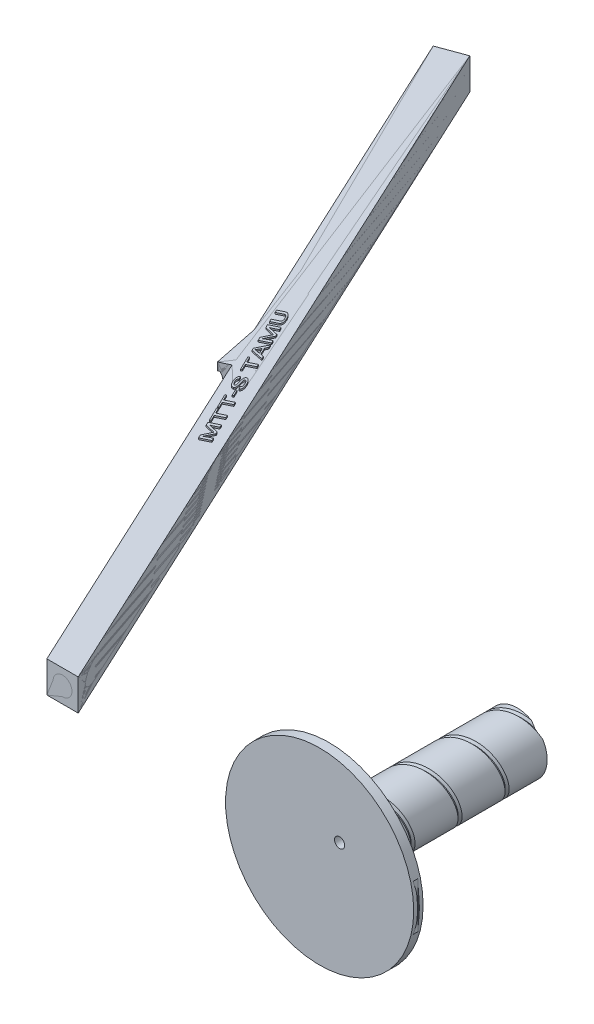
SolidWorks part; units mm, degrees
other "Markup1"
sketch "Sketch47" plane through (-252.8035, -252.8035, 139.7467) normal (0, 0, 1) x (-1, 0, 0)
ref_plane "Front Plane" through (0, 0, 0) normal (1, 0, 0) x (0, 1, 0)
ref_plane "Top Plane" through (0, 0, 0) normal (0, 0, 1) x (0, 1, 0)
ref_plane "Right Plane" through (0, 0, 0) normal (0, 1, 0) x (-1, 0, 0)
sketch "Sketch8" plane through (0, 0, 0) normal (0, 0, 1) x (0, 1, 0)
  circle A0 centre (0, 0) radius 9.55
  dimension "D1" = 19.1
extrude "HelicalLength" add sketch "Sketch8" along normal blind 60 separate body
thread "WireThreads" pitch 1.5 method cut profile "Thread Profile1" start angle 14, offset 2, length 160, pitch 15, diameter 19.1
ref_plane "Plane1" through (9.2663, 2.3104, -2) normal (0.2419, -0.9703, 0) x (0.9703, 0.2419, 0)
sketch "Thread Profile1" plane through (9.2663, 2.3104, -2) normal (0.2419, -0.9703, 0) x (0.9703, 0.2419, 0)
  line L0 (0, 0) -> (0, 1.5) construction
  line L11 (0, 0) -> (0, 1.3125)
  line L12 (0, 1.3125) -> (-0.8119, 0.8437)
  line L13 (-0.8119, 0.8437) -> (-0.8119, 0.4687)
  line L15 (-0.8119, 0.4687) -> (0, 0)
  line L17 (-0.8119, 0.6562) -> (0, 0.6562) construction
  point P2 (0, 0)
  dimension "Pitch" = 1.5
  dimension "Profile_Angle" = 60
  dimension "Profile_Land" = 0.375
  dimension "Profile_Height" = 0.8119
sketch "Sketch12" plane through (0, 0, 0) normal (0, 0, 1) x (0, 1, 0)
  circle A0 centre (0, 0) radius 8
extrude "Cut-Extrude1" cut sketch "Sketch12" along normal blind 60
sketch "Sketch14" plane through (0, 0, 60) normal (0, 0, 1) x (0, -1, 0)
  circle A0 centre (0, 0) radius 30
extrude "Top of Helical" add sketch "Sketch14" along normal blind 3 contours A0
sketch "Supports" plane through (0, 0, 0) normal (0, 1, 0) x (-1, 0, 0)
  line L2 (83.0856, 56.8881) -> (192.1707, -177.0456)
  line L11 (200.7103, -173.9139) -> (93.0856, 56.8881)
  line L12 (93.0856, 56.8881) -> (83.0856, 56.8881)
  line L13 (192.1707, -177.0456) -> (200.7103, -173.9139)
  line L15 (144.6827, -53.7621) -> (147.8613, -52.2799)
  line L16 (147.8613, -52.2799) -> (150.8999, -67.095)
  line L18 (150.8999, -67.095) -> (144.6827, -53.7621)
  point P0 (0, 0)
  point P1 (0, 0)
  point P2 (0, 0)
extrude "Support" add sketch "Supports" along normal mid plane 10 contours L2 L13 L11 L12 | L16 L15 L11
sketch "Sketch18" plane through (0, 0, 63) normal (0, 0, 1) x (0, -1, 0)
  circle A0 centre (-7.0243, 6.3716) radius 1.6161
extrude "SMAHole" cut sketch "Sketch18" against normal blind 3
sketch "Sketch30" plane through (0, 0, 0) normal (1, 0, 0) x (0, 1, 0)
  line L0 (150.6912, -172.7061) -> (149.5087, -173.9919)
  line L1 (0, -188.7392) -> (0, 188.7392) construction
  line L2 (-150.6912, -172.7061) -> (-149.5087, -173.9919)
sketch "Sketch40" plane through (0, 0, 0) normal (0, 1, 0) x (-1, 0, 0)
  line L0 (0, 189.6665) -> (0, -189.6665) construction
  line L1 (-30.0176, 61.2136) -> (-30.0176, 61.7977)
  line L2 (-29.7091, 61.7977) -> (-30.0176, 61.7977)
  line L3 (-29.0913, 62.3087) -> (-29.7091, 61.7977)
  line L4 (-29.0913, 60.7506) -> (-29.0913, 62.3087)
  line L5 (30.0176, 61.2136) -> (29.6894, 61.2136)
  line L6 (29.6894, 61.2136) -> (29.0913, 60.7506)
  line L7 (29.0913, 60.7506) -> (29.0913, 62.3087)
  line L8 (29.0913, 62.3087) -> (29.7091, 61.7977)
  line L9 (29.7091, 61.7977) -> (30.0176, 61.7977)
  line L10 (30.0176, 61.2136) -> (30.0176, 61.7977)
  line L11 (-29.6894, 61.2136) -> (-29.0913, 60.7506)
  line L12 (-30.0176, 61.2136) -> (-29.6894, 61.2136)
extrude "Cut-Extrude6" cut sketch "Sketch40" against normal mid plane 30
sketch "Sketch41" plane through (-46.4333, 0, -99.5766) normal (0.4226, 0, 0.9063) x (0.9063, 0, -0.4226)
  circle A0 centre (-115.2305, 0) radius 4.6444
extrude "Cut-Extrude7" cut sketch "Sketch41" against normal blind 15
sketch "Sketch42" plane through (0, 5, 0) normal (0, 1, 0) x (-1, 0, 0)
  line L0 (126.2063, -28.5433) -> (156.3015, -91.4697) construction
  text T0 "<b>MTT-S TAMU</b>" font "Roboto" height 3.175
sketch "Sketch43" plane through (0, 5, 0) normal (0, 1, 0) x (-1, 0, 0)
  line L0 (101.9085, 20.9352) -> (104.9898, 21.8732)
  line L1 (104.9898, 21.8732) -> (103.2157, 19.5777)
  line L2 (103.2157, 19.5777) -> (106.1118, 19.4956)
  line L3 (106.1118, 19.4956) -> (103.4237, 17.7047)
  line L4 (103.4237, 17.7047) -> (103.3006, 18.002)
  line L5 (103.3006, 18.002) -> (105.2049, 19.233)
  line L6 (105.2049, 19.233) -> (102.6528, 19.3054)
  line L7 (102.6528, 19.3054) -> (104.2052, 21.3141)
  line L8 (104.2052, 21.3141) -> (102.0446, 20.6563)
  line L9 (102.0446, 20.6563) -> (101.9085, 20.9352)
  line L10 (104.0107, 16.514) -> (106.5727, 17.7315)
  line L11 (106.5727, 17.7315) -> (106.8818, 17.0809)
  line L12 (106.8818, 17.0809) -> (107.1603, 17.2133)
  line L13 (107.1603, 17.2133) -> (106.4169, 18.7774)
  line L14 (106.4169, 18.7774) -> (106.1419, 18.6467)
  line L15 (106.1419, 18.6467) -> (106.4409, 18.0177)
  line L16 (106.4409, 18.0177) -> (103.8755, 16.7985)
  line L17 (103.8755, 16.7985) -> (104.0107, 16.514)
  line L18 (106.9455, 16.9655) -> (107.25, 16.3249)
  line L19 (107.25, 16.3249) -> (104.6808, 15.1039)
  line L20 (104.6808, 15.1039) -> (104.8254, 14.7998)
  line L21 (104.8254, 14.7998) -> (107.3884, 16.0179)
  line L22 (107.3884, 16.0179) -> (107.6844, 15.3948)
  line L23 (107.6844, 15.3948) -> (107.9593, 15.5255)
  line L24 (107.9593, 15.5255) -> (107.2149, 17.0917)
  line L25 (107.2149, 17.0917) -> (106.9455, 16.9655)
  line L26 (106.5727, 12.8032) -> (106.3025, 12.9886)
  line L27 (109.0001, 12.2749) -> (108.7224, 12.4151)
  line L28 (109.7957, 10.8368) -> (110.1001, 10.1962)
  line L29 (110.1001, 10.1962) -> (107.531, 8.9752)
  line L30 (107.531, 8.9752) -> (107.6755, 8.6712)
  line L31 (107.6755, 8.6712) -> (110.2385, 9.8892)
  line L32 (110.2385, 9.8892) -> (110.5346, 9.2662)
  line L33 (110.5346, 9.2662) -> (110.8094, 9.3968)
  line L34 (110.8094, 9.3968) -> (110.0651, 10.963)
  line L35 (110.0651, 10.963) -> (109.7957, 10.8368)
  line L36 (109.4678, 4.7772) -> (112.5491, 5.7152)
  line L37 (112.5491, 5.7152) -> (110.775, 3.4198)
  line L38 (110.775, 3.4198) -> (113.6711, 3.3376)
  line L39 (113.6711, 3.3376) -> (110.9831, 1.5467)
  line L40 (110.9831, 1.5467) -> (110.8599, 1.8441)
  line L41 (110.8599, 1.8441) -> (112.7642, 3.0751)
  line L42 (112.7642, 3.0751) -> (110.2121, 3.1475)
  line L43 (110.2121, 3.1475) -> (111.7646, 5.1561)
  line L44 (111.7646, 5.1561) -> (109.6039, 4.4984)
  line L45 (109.6039, 4.4984) -> (109.4678, 4.7772)
  line L46 (109.6778, 7.5921) -> (110.9514, 7.5921)
  line L47 (110.9514, 7.5921) -> (110.1423, 6.596)
  line L48 (110.1423, 6.596) -> (109.6778, 7.5921)
  line L49 (108.2031, 7.5921) -> (109.3354, 7.5921)
  line L50 (109.3354, 7.5921) -> (109.9101, 6.3599)
  line L51 (109.9101, 6.3599) -> (109.1793, 5.4602)
  line L52 (109.1793, 5.4602) -> (109.3354, 5.1255)
  line L53 (109.3354, 5.1255) -> (111.6176, 7.8904)
  line L54 (111.6176, 7.8904) -> (108.0755, 7.8904)
  line L55 (108.0755, 7.8904) -> (108.2031, 7.5921)
  line L56 (114.1273, 2.3932) -> (114.2581, 2.1081)
  line L57 (114.8933, 0.7892) -> (115.0089, 0.4737)
  line L58 (106.3776, 14.5474) -> (106.8818, 13.4741)
  line L59 (106.8818, 13.4741) -> (106.6452, 13.3629)
  line L60 (106.6452, 13.3629) -> (106.1346, 14.4333)
  line L61 (106.1346, 14.4333) -> (106.3776, 14.5474)
  spline S0 degree 3 poles (109.0001, 12.2749) (109.3075, 12.5936) (109.2657, 13.5749) (108.1151, 13.7916) (107.6133, 13.0938) (107.5354, 12.4103) (107.2883, 11.5281) (106.4624, 11.6885) (106.2609, 12.2706) (106.4283, 12.618) (106.5727, 12.8032) knots 0 0 0 0 0.216001 0.35012 0.454376 0.59346 0.711588 0.832522 0.880345 1 1 1 1
  spline S1 degree 3 poles (106.3025, 12.9886) (106.1901, 12.7865) (105.9616, 12.4602) (106.0391, 11.9135) (106.2897, 11.5153) (106.8216, 11.2348) (107.4632, 11.4221) (107.798, 11.9958) (107.9019, 12.5768) (107.972, 13.1456) (108.4276, 13.4453) (108.9775, 13.1301) (108.8433, 12.6139) (108.7224, 12.4151) knots 0 0 0 0 0.1187 0.173526 0.2599 0.338136 0.450558 0.543453 0.645861 0.740559 0.809819 0.869876 1 1 1 1
  spline S2 degree 3 poles (114.2581, 2.1081) (113.715, 1.888) (113.0487, 1.4788) (112.0912, 1.1645) (111.7302, 0.563) (112.0143, -0.1302) (112.7205, -0.2875) (113.2591, -0.0031) (113.9715, 0.3535) (114.5303, 0.5875) (114.8933, 0.7892) knots 0 0 0 0 0.260538 0.35717 0.440729 0.545307 0.639288 0.729165 0.812848 1 1 1 1
  spline S3 degree 1 poles (114.1273, 2.3932) (111.9971, 1.3732) knots 0 0 1 1
  spline S4 degree 3 poles (111.9971, 1.3732) (111.7415, 1.2483) (111.4568, 0.7434) (111.5918, -0.0275) (112.0746, -0.5136) (112.7345, -0.603) (113.3001, -0.2829) (114.0989, -0.0068) (114.6079, 0.37) (115.0089, 0.4737) knots 0 0 0 0 0.15463 0.301164 0.410595 0.521219 0.649696 0.769002 1 1 1 1
extrude "Cut-Extrude8" cut sketch "Sketch43" against normal blind 1.5
extrude "Boss-Extrude20" add sketch "Supports<3>" along normal mid plane 10 separate body contours L16 L18 L15 | L12 L2 L13 L11
sketch "Supports<3>" plane through (0, 0, 0) normal (0, 1, 0) x (-1, 0, 0) same geometry as "Supports"
sketch "Sketch46" plane through (0, 0, 56.8881) normal (0, 0, 1) x (1, 0, 0)
  line L0 (-93.0856, 0) -> (-83.0856, 0) construction
  circle A0 centre (-88.0856, 0) radius 3
extrude "Boss-Extrude23" add sketch "Sketch42" along normal blind 0.5
extrude "Cut-Extrude9" cut sketch "Sketch46" against normal blind 10 contours A0
sketch "Sketch48" plane through (-80.0115, 0, -218.1774) normal (-0.3443, 0, -0.9389) x (0.9389, 0, -0.3443)
  line L0 (-119.4634, 0) -> (-128.5592, 0) construction
  circle A0 centre (-124.0113, 0) radius 3
extrude "Cut-Extrude10" cut sketch "Sketch48" against normal blind 10
sketch "Sketch49" plane through (-46.4333, 0, -99.5766) normal (0.4226, 0, 0.9063) x (0.9063, 0, -0.4226)
  line L0 (-108.4062, 0) -> (-111.9134, 0) construction
  circle A0 centre (-111.4716, 0) radius 2.54
extrude "Cut-Extrude11" cut sketch "Sketch49" against normal blind 15 contours A0
